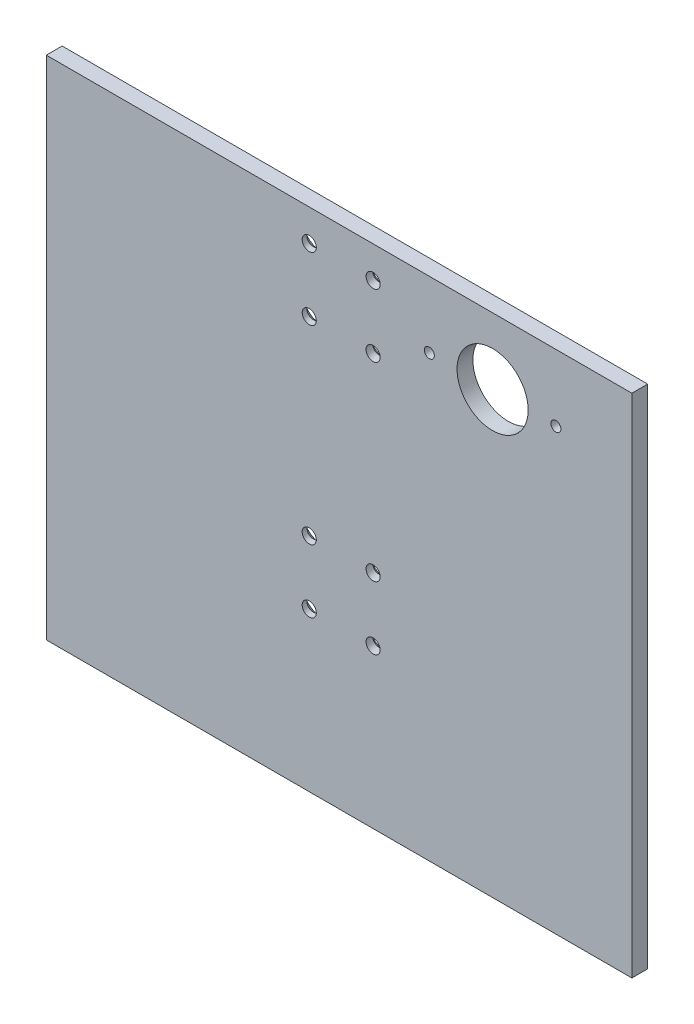
SolidWorks part; units mm, degrees
material "PC High Viscosity"
ref_plane "Front Plane" through (0, 0, 0) normal (0, 0, 1) x (1, 0, 0)
ref_plane "Top Plane" through (0, 0, 0) normal (0, 1, 0) x (1, 0, 0)
ref_plane "Right Plane" through (0, 0, 0) normal (1, 0, 0) x (0, 0, -1)
sketch "Sketch1" plane through (0, 0, 0) normal (0, 0, 1) x (1, 0, 0)
  line L1 (-117.475, -101.6) -> (117.475, -101.6)
  line L2 (-117.475, -101.6) -> (-117.475, 101.6)
  line L3 (-117.475, 101.6) -> (117.475, 101.6)
  line L4 (117.475, -101.6) -> (117.475, 101.6)
  line L5 (-117.475, -101.6) -> (117.475, 101.6) construction
  line L6 (-117.475, 101.6) -> (117.475, -101.6) construction
  point P0 (0, 0)
  dimension "D1" = 234.95
  dimension "D2" = 203.2
extrude "Boss-Extrude1" add sketch "Sketch1" along normal blind 6.35
sketch "Sketch2" plane through (0, 0, 6.35) normal (0, 0, 1) x (1, 0, 0)
  line L0 (117.475, 101.6) -> (-117.475, 101.6) construction
  line L1 (117.475, -101.6) -> (117.475, 101.6) construction
  circle A0 centre (61.595, 74.93) radius 14.2748
  dimension "D3" = 28.5496
  dimension "D1" = 26.67
  dimension "D2" = 55.88
extrude "Cut-Extrude1" cut sketch "Sketch2" against normal through all
hole_wizard "CSK for #10 Flat Head Machine Screw (100)1" positions "Sketch3" profile "Sketch4" countersink size "#10" standard "ANSI Inch" end condition through all
sketch "Sketch3" plane through (292.077, -265.5951, -43.8004) normal (0.1349, 0, 0.9909) x (0.9909, 0, -0.1349)
  point P0 (-308.0419, 227.4951)
  point P2 (-308.0419, 252.8951)
  point P4 (-308.042, 329.0951)
  point P6 (-308.042, 354.4951)
sketch "Sketch4" plane through (-13.1497, -38.1, -2.2498) normal (0, 1, 0) x (-0.9909, 0, 0.1349)
  line L0 (0, 0) -> (0, 26.1406)
  line L1 (0, 26.1406) -> (2.8067, 26.1406)
  line L2 (2.8067, 26.1406) -> (2.8067, 6.0833)
  line L3 (2.8067, 6.0833) -> (8.89, 0)
  line L4 (8.89, 0) -> (0, 0)
  line L5 (-2.8067, 6.0833) -> (-8.89, 0) construction
  line L6 (0, -6.35) -> (0, 107.95) construction
  dimension "Thru Hole Dia." = 5.6134
  dimension "Thru Hole Depth" = 26.1406
  dimension "Near C'Sink Dia." = 17.78
  dimension "Near C'Sink Angle" = 90
hole_wizard "CSK for #10 Flat Head Machine Screw (100)2" positions "Sketch5" profile "Sketch6" countersink size "#10" standard "ANSI Inch" end condition through all
sketch "Sketch5" plane through (292.4196, -265.5951, -41.2836) normal (0.1349, 0, 0.9909) x (0.9909, 0, -0.1349)
  point P0 (-282.6419, 227.4951)
  point P2 (-282.6419, 252.8951)
  point P4 (-282.642, 329.0951)
  point P6 (-282.642, 354.4951)
sketch "Sketch6" plane through (12.3608, -38.1, -3.1591) normal (0, 1, 0) x (-0.9909, 0, 0.1349)
  line L0 (0, 0) -> (0, 23.6006)
  line L1 (0, 23.6006) -> (2.8067, 23.6006)
  line L2 (2.8067, 23.6006) -> (2.8067, 6.0833)
  line L3 (2.8067, 6.0833) -> (8.89, 0)
  line L4 (8.89, 0) -> (0, 0)
  line L5 (-2.8067, 6.0833) -> (-8.89, 0) construction
  line L6 (0, -6.35) -> (0, 107.95) construction
  dimension "Thru Hole Dia." = 5.6134
  dimension "Thru Hole Depth" = 23.6006
  dimension "Near C'Sink Dia." = 17.78
  dimension "Near C'Sink Angle" = 90
sketch "Sketch10" plane through (0, 0, 0) normal (0, 0, -1) x (-1, 0, 0)
  line L0 (-117.475, -101.6) -> (-117.475, 101.6) construction
  line L1 (-117.475, 101.6) -> (117.475, 101.6) construction
  arc A0 (-36.1906, 72.9667) -> (-36.1995, 77.0053) centre (-36.1951, 74.986) ccw construction
  arc A1 (-36.1995, 77.0053) -> (-36.1906, 72.9667) centre (-36.1951, 74.986) ccw construction
  arc A2 (-86.9905, 72.8547) -> (-86.9994, 76.8933) centre (-86.9949, 74.874) ccw construction
  arc A3 (-86.9994, 76.8933) -> (-86.9905, 72.8547) centre (-86.9949, 74.874) ccw construction
  arc A4 (-36.1906, 72.9667) -> (-36.1995, 77.0053) centre (-36.1951, 74.986) ccw
  arc A5 (-36.1995, 77.0053) -> (-36.1906, 72.9667) centre (-36.1951, 74.986) ccw
  arc A6 (-86.9905, 72.8547) -> (-86.9994, 76.8933) centre (-86.9949, 74.874) ccw
  arc A7 (-86.9994, 76.8933) -> (-86.9905, 72.8547) centre (-86.9949, 74.874) ccw
  dimension "D1" = 81.2799
  dimension "D2" = 30.4801
  dimension "D3" = 26.614
extrude "Cut-Extrude2" cut sketch "Sketch10" against normal through all
